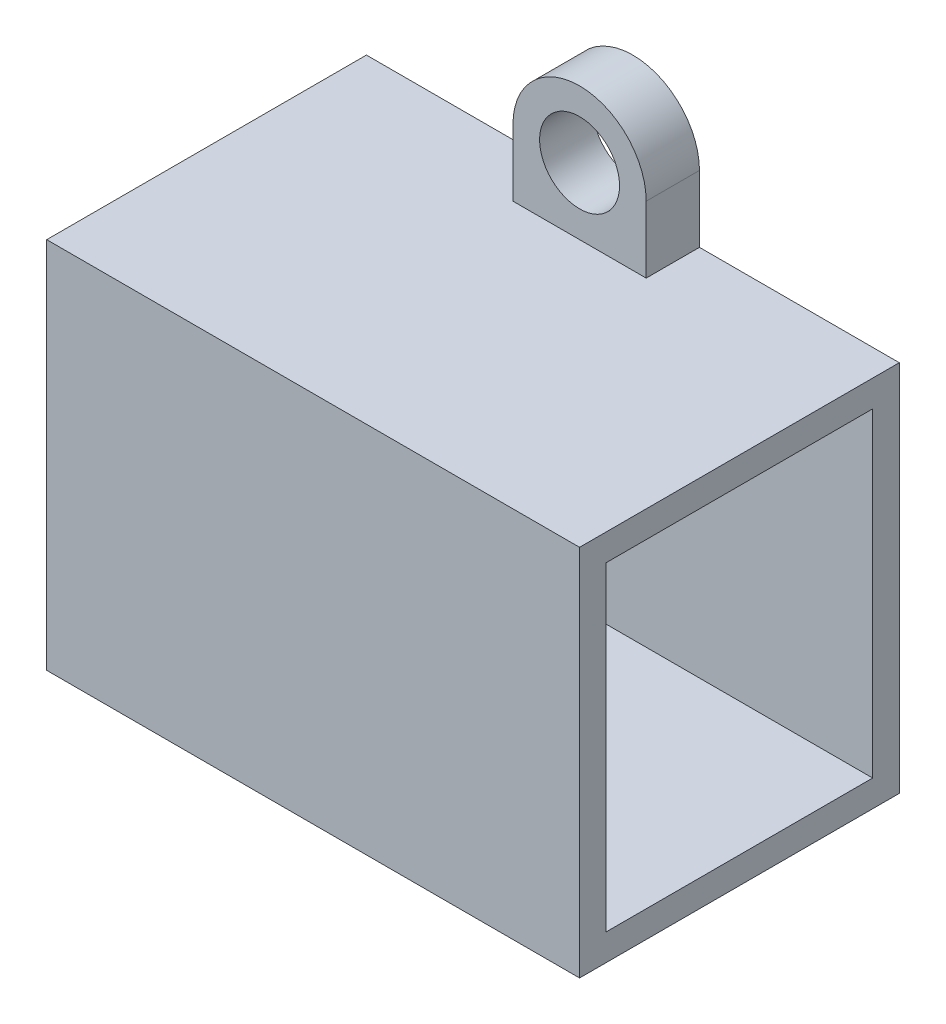
SolidWorks part; units mm, degrees
ref_plane "Ön Düzlem" through (0, 0, 0) normal (0, 0, 1) x (1, 0, 0)
ref_plane "Üst Düzlem" through (0, 0, 0) normal (0, 1, 0) x (1, 0, 0)
ref_plane "Sağ Düzlem" through (0, 0, 0) normal (1, 0, 0) x (0, 0, -1)
sketch "Sketch1" plane through (0, 0, 0) normal (0, 0, 1) x (1, 0, 0)
  line L1 (-10, 7) -> (10, 7)
  line L2 (-10, 7) -> (-10, -7)
  line L3 (-10, -7) -> (10, -7)
  line L4 (10, 7) -> (10, -7)
  line L5 (-10, 7) -> (10, -7) construction
  line L6 (-10, -7) -> (10, 7) construction
  point P0 (0, 0)
  dimension "D1" = 20
  dimension "D2" = 14
extrude "Boss-Extrude1" add sketch "Sketch1" along normal blind 12
sketch "Sketch2" plane through (0, 0, 0) normal (0, 0, 1) x (1, 0, 0)
  line L0 (10, 7) -> (-10, 7) construction
  line L1 (-10, -7) -> (10, -7) construction
  line L2 (2.5, -9.5) -> (2.5, -7)
  line L3 (-2.5, -9.5) -> (-2.5, -7)
  line L4 (2.5, 9.5) -> (2.5, 7)
  line L5 (-2.5, 9.5) -> (-2.5, 7)
  line L6 (-2.5, 7) -> (2.5, 7)
  line L7 (-2.5, -7) -> (2.5, -7)
  arc A0 (2.5, 9.5) -> (-2.5, 9.5) centre (0, 9.5) ccw
  arc A1 (-2.5, -9.5) -> (2.5, -9.5) centre (0, -9.5) ccw
  circle A2 centre (0, 9.5) radius 1.5
  circle A3 centre (0, -9.5) radius 1.5
  dimension "D1" = 19
extrude "Boss-Extrude2" add sketch "Sketch2" along normal blind 2
shell "Shell2" thickness 1 removed face at (10, 0, 6) removed face at (-10, 0, 6)
